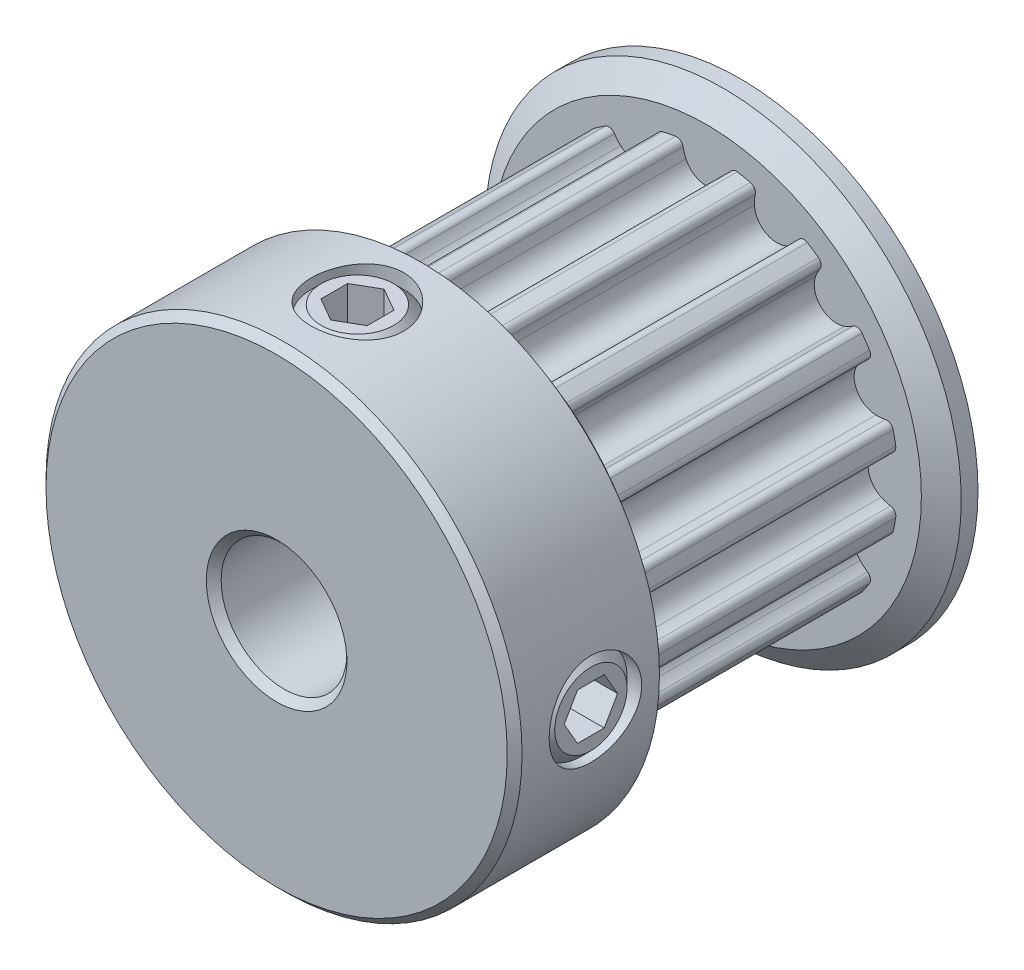
SolidWorks part; units mm, degrees
ref_plane "Front Plane" through (0, 0, 0) normal (0, 0, 1) x (1, 0, 0)
ref_plane "Top Plane" through (0, 0, 0) normal (0, 1, 0) x (1, 0, 0)
ref_plane "Right Plane" through (0, 0, 0) normal (1, 0, 0) x (0, 0, -1)
sketch "Sketch1" plane through (0, 0, 0) normal (0, 0, 1) x (1, 0, 0)
  line L1 (-2.553, 6.1245) -> (2.553, 6.1245) construction
  line L4 (0, 0) -> (0, 6.1245) construction
  line L5 (0, 6.1245) -> (0, 12.064) construction
  line L6 (0, 7.6455) -> (2.9417, 7.0569) construction
  line L7 (2.9417, 7.0569) -> (3.8741, 6.6682) construction
  line L8 (2.9417, 7.0569) -> (2.553, 6.1245) construction
  line L9 (-2.9417, 7.0569) -> (-2.553, 6.1245) construction
  line L10 (-2.7951, 6.7052) -> (-3.7579, 9.015)
  line L11 (-3.7579, 9.015) -> (3.7579, 9.015)
  line L12 (3.7579, 9.015) -> (2.7951, 6.7052)
  circle A0 centre (0, 0) radius 7.6455 construction
  circle A1 centre (0, 0) radius 9.015 construction
  circle A2 centre (0, 0) radius 7.2645 construction
  arc A3 (-0.7739, 6.6229) -> (0.7739, 6.6229) centre (0, 6.9745) ccw
  arc A4 (-0.7739, 6.6229) -> (-0.8836, 6.9694) centre (0.61, 7.2516) cw
  arc A5 (-2.7951, 6.7052) -> (-1.1695, 7.1697) centre (0, 0) cw
  arc A6 (-0.8836, 6.9694) -> (-1.1695, 7.1697) centre (-1.1292, 6.923) ccw
  arc A7 (2.7951, 6.7052) -> (1.1695, 7.1697) centre (0, 0) ccw
  arc A8 (0.8836, 6.9694) -> (1.1695, 7.1697) centre (1.1292, 6.923) cw
  arc A9 (0.7739, 6.6229) -> (0.8836, 6.9694) centre (-0.61, 7.2516) ccw
  point P6 (0, 20.9083)
  point P11 (0, 7.6455)
  point P13 (0, 9.015)
  point P14 (0, 7.2645)
  dimension "D1" = 8.8444
  dimension "D2" = 4.4185
sketch "Sketch2" plane through (0, 0, 0) normal (1, 0, 0) x (0, 0, -1)
  line L0 (-8.775, 2.3812) -> (8.775, 2.3812)
  line L1 (-8.775, 2.3812) -> (-8.775, 9.015)
  line L2 (-3.29, 9.015) -> (-8.775, 9.015)
  line L3 (-3.925, 2.3813) -> (-3.925, 9.015) construction
  line L4 (-3.925, 9.015) -> (-2.655, 9.015) construction
  line L5 (-2.655, 9.015) -> (-2.655, 7.2645) construction
  line L6 (-2.655, 7.2645) -> (7.505, 7.2645)
  line L7 (7.505, 7.2645) -> (7.505, 9.015) construction
  line L8 (7.505, 9.015) -> (8.775, 9.015) construction
  line L9 (8.775, 9.015) -> (8.775, 2.3812)
  line L10 (-8.775, 0) -> (8.775, 0) construction
  line L11 (8.14, 9.015) -> (7.505, 8.1398)
  line L12 (-2.655, 8.1398) -> (-3.29, 9.015)
  line L14 (-2.655, 8.1398) -> (-2.655, 7.2645)
  line L15 (7.505, 7.2645) -> (7.505, 8.1398)
  line L16 (8.14, 9.015) -> (8.775, 9.015)
  arc A0 (-2.655, 8.1398) -> (-3.29, 9.015) centre (-3.5757, 8.1398) ccw construction
  arc A1 (7.505, 8.1398) -> (8.14, 9.015) centre (8.4257, 8.1398) cw construction
  point P12 (-2.655, 8.1398)
  point P14 (-3.29, 9.015)
  point P20 (7.505, 8.1398)
  point P21 (8.14, 9.015)
  point P25 (7.505, 0)
  point P26 (-2.655, 0)
  dimension "OA" = 17.55
  dimension "Bore" = 4.7625
  dimension "Outside Width" = 11.43
  dimension "Inside Width" = 10.16
revolve "Revolve1" add sketch "Sketch2" angle 360 mid plane about L10
sketch "Sketch3" plane through (0, 0, 0) normal (0, 0, 1) x (1, 0, 0)
  line L6 (3.7579, 9.015) -> (-3.7579, 9.015)
  line L7 (2.7951, 6.7052) -> (3.7579, 9.015)
  line L8 (-3.7579, 9.015) -> (-2.7951, 6.7052)
  line L9 (3.7579, 9.015) -> (-3.7579, 9.015)
  line L10 (2.7951, 6.7052) -> (3.7579, 9.015)
  line L11 (-3.7579, 9.015) -> (-2.7951, 6.7052)
  arc A8 (2.7951, 6.7052) -> (1.1695, 7.1697) centre (0, 0) ccw
  arc A9 (1.1695, 7.1697) -> (0.8836, 6.9694) centre (1.1292, 6.923) ccw
  arc A10 (0.7739, 6.6229) -> (0.8836, 6.9694) centre (-0.61, 7.2516) ccw
  arc A11 (-0.7739, 6.6229) -> (0.7739, 6.6229) centre (0, 6.9745) ccw
  arc A12 (-0.8836, 6.9694) -> (-0.7739, 6.6229) centre (0.61, 7.2516) ccw
  arc A13 (-0.8836, 6.9694) -> (-1.1695, 7.1697) centre (-1.1292, 6.923) ccw
  arc A14 (-1.1695, 7.1697) -> (-2.7951, 6.7052) centre (0, 0) ccw
  arc A15 (2.7951, 6.7052) -> (1.1695, 7.1697) centre (0, 0) ccw
  arc A16 (1.1695, 7.1697) -> (0.8836, 6.9694) centre (1.1292, 6.923) ccw
  arc A17 (0.7739, 6.6229) -> (0.8836, 6.9694) centre (-0.61, 7.2516) ccw
  arc A18 (-0.7739, 6.6229) -> (0.7739, 6.6229) centre (0, 6.9745) ccw
  arc A19 (-0.8836, 6.9694) -> (-0.7739, 6.6229) centre (0.61, 7.2516) ccw
  arc A20 (-0.8836, 6.9694) -> (-1.1695, 7.1697) centre (-1.1292, 6.923) ccw
  arc A21 (-1.1695, 7.1697) -> (-2.7951, 6.7052) centre (0, 0) ccw
  dimension "D1" = 0
extrude "Cut-Extrude1" cut sketch "Sketch3" against normal up to vertex (7.505 mm away) from vertex up to point (0, 7.2645, -7.505) starting at point (0, 7.2645, 2.655)
pattern_circular "CirPattern1" count 16 over 360 about axis through (0, 0, 8.775) along (0, 0, 1) of "Cut-Extrude1"
sketch "Sketch4" plane through (0, 0, 0) normal (1, 0, 0) x (0, -1, 0)
  line L0 (0, -2.655) -> (0, -8.775) construction
  line L1 (-2.3812, -8.775) -> (2.3812, -8.775) construction
  line L2 (8.1398, -2.655) -> (-8.1398, -2.655) construction
  circle A0 centre (0, -5.715) radius 1.7526
extrude "Cut-Extrude2" cut sketch "Sketch4" along normal through all
ref_plane "Plane1" through (0, 0, 5.715) normal (0, 0, 1) x (1, 0, 0)
sketch "Sketch5" plane through (0, 0, 5.715) normal (0, 0, 1) x (1, 0, 0)
  line L0 (0, 0) -> (0, 9.015) construction
  line L1 (2.3812, -1.3716) -> (2.3812, 0)
  line L2 (2.7622, -1.7526) -> (8.462, -1.7526)
  line L3 (2.3812, 0) -> (9.015, 0) construction
  line L4 (2.3812, 0) -> (8.843, 0)
  line L5 (8.843, 0) -> (8.843, -1.3716)
  line L6 (2.7622, -1.7526) -> (2.3812, -1.3716)
  line L7 (8.843, -1.3716) -> (8.462, -1.7526)
  circle A0 centre (0, 0) radius 9.015 construction
  circle A1 centre (0, 0) radius 2.3812 construction
  point P2 (2.3812, -1.7526)
  point P11 (8.843, -1.7526)
revolve "Revolve2" add sketch "Sketch5" angle 360 mid plane about L4
sketch "Sketch6" plane through (8.843, 5.3841, 0) normal (-1, 0, 0) x (0, -1, 0)
  line L1 (5.3841, 6.7269) -> (4.5078, 6.2209)
  line L2 (4.5078, 6.2209) -> (4.5078, 5.2091)
  line L3 (4.5078, 5.2091) -> (5.3841, 4.7031)
  line L4 (5.3841, 4.7031) -> (6.2604, 5.2091)
  line L5 (6.2604, 5.2091) -> (6.2604, 6.2209)
  line L6 (6.2604, 6.2209) -> (5.3841, 6.7269)
  circle A0 centre (5.3841, 5.715) radius 0.8763 construction
  dimension "D1" = 1.7526
extrude "Cut-Extrude3" cut sketch "Sketch6" along normal blind 1.3144
pattern_circular "CirPattern3" count 2 over 90 about axis through (0, 0, 8.775) along (0, 0, 1) of "Cut-Extrude2", "Revolve2", "Cut-Extrude3"
chamfer "Chamfer1" distance 0.2807 angle 45 2 edges at (2.3812, 0, 8.775) (9.015, 0, 8.775)
ref_axis "Center Axis 1" through (0, 0, -8.775) along (0, 0, 1)
ref_plane "Contact Plane 1" through (0, 0, 8.775) normal (0, 0, 1) x (1, 0, 0)
ref_plane "Contact Plane 2" through (0, 0, -8.775) normal (0, 0, -1) x (-1, 0, 0)
equation "\"D2@Sketch1\"= \"D1@Sketch1\" / 2"
equation "\"D1@Sketch6\" = \"Set Screw@Sketch4\" / 2"
equation "\"D1@Cut-Extrude3\" = \"D1@Sketch6\"*.75"
